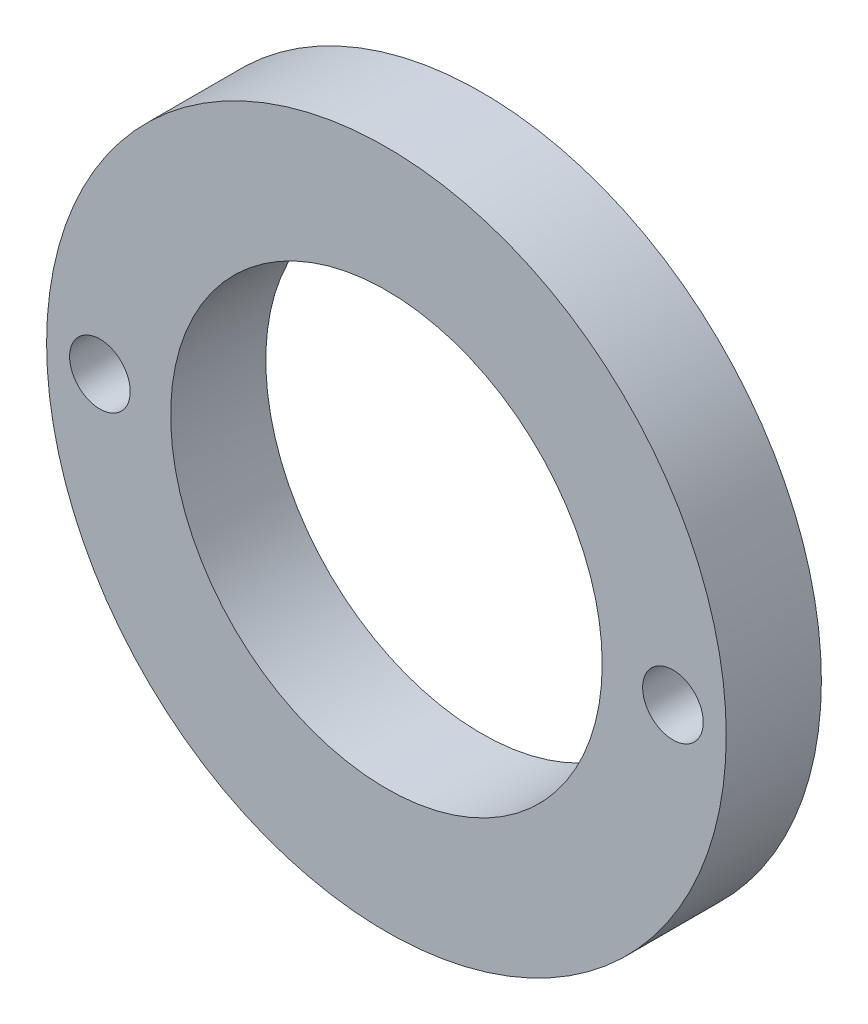
SolidWorks part; units mm, degrees
ref_plane "Front Plane" through (0, 0, 0) normal (0, 0, 1) x (1, 0, 0)
ref_plane "Top Plane" through (0, 0, 0) normal (0, 1, 0) x (1, 0, 0)
ref_plane "Right Plane" through (0, 0, 0) normal (1, 0, 0) x (0, 0, -1)
sketch "Sketch1" plane through (0, 0, 0) normal (0, 0, 1) x (1, 0, 0)
  circle A0 centre (0, 0) radius 20
  circle A1 centre (0, 0) radius 12.7
  dimension "D1" = 25.4
  dimension "D2" = 40
extrude "Boss-Extrude1" add sketch "Sketch1" along normal blind 5.6 contours A0 | A1
hole_wizard "#28 (0.1405) Diameter Hole1" positions "Sketch5" profile "Sketch4" hole size "#28" standard "ANSI Inch" end condition through all
sketch "Sketch5" plane through (0, 0, 5.6) normal (0, 0, 1) x (1, 0, 0)
  point P0 (-16.8627, 0)
  point P3 (16.8627, 0)
  point P6 (16.8627, 0)
sketch "Sketch4" plane through (-16.8627, 0, 5.6) normal (1, 0, 0) x (0, -1, 0)
  line L0 (0, 0) -> (0, 5.6)
  line L1 (0, 5.6) -> (1.7843, 5.6)
  line L2 (1.7843, 5.6) -> (1.7843, 0)
  line L5 (1.7843, 0) -> (0, 0)
  line L11 (0, -6.35) -> (0, 107.95) construction
  dimension "Thru Hole Dia." = 3.5687
  dimension "Thru Hole Depth" = 5.6
